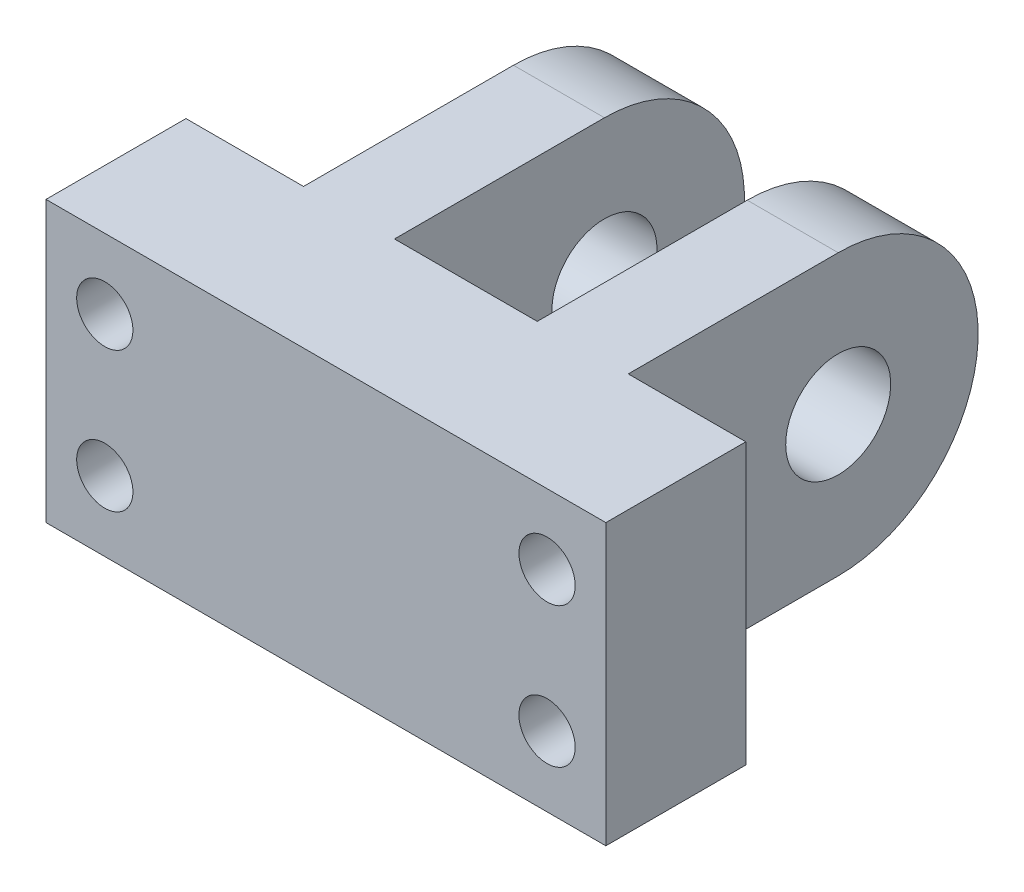
SolidWorks part; units mm, degrees
ref_plane "Front Plane" through (0, 0, 0) normal (0, 0, 1) x (1, 0, 0)
ref_plane "Top Plane" through (0, 0, 0) normal (0, 1, 0) x (1, 0, 0)
ref_plane "Right Plane" through (0, 0, 0) normal (1, 0, 0) x (0, 0, -1)
sketch "Sketch1" plane through (0, 0, 0) normal (1, 0, 0) x (0, 0, -1)
  line L1 (0, 0) -> (31.75, 0)
  line L2 (0, 0) -> (0, 25.4)
  line L3 (0, 25.4) -> (31.75, 25.4)
  circle A0 centre (31.75, 12.7) radius 4.7625
  arc A1 (31.75, 25.4) -> (31.75, 0) centre (31.75, 12.7) cw
  dimension "D1" = 9.525
  dimension "D3" = 12.7
  dimension "D2" = 31.75
extrude "Boss-Extrude1" add sketch "Sketch1" along normal blind 50.8
sketch "Sketch2" plane through (0, 0, 0) normal (0, -1, 0) x (1, 0, 0)
  line L0 (50.8, -12.7) -> (40.132, -12.7)
  line L1 (50.8, 0) -> (50.8, -31.75) construction
  line L2 (40.132, -12.7) -> (40.132, -44.45)
  line L3 (40.132, -44.45) -> (31.877, -44.45)
  line L4 (31.877, -44.45) -> (31.877, -12.7)
  line L5 (31.877, -12.7) -> (18.923, -12.7)
  line L6 (18.923, -12.7) -> (18.923, -44.45)
  line L7 (18.923, -44.45) -> (10.668, -44.45)
  line L8 (10.668, -44.45) -> (10.668, -12.7)
  line L9 (10.668, -12.7) -> (0, -12.7)
  line L10 (0, 0) -> (0, -31.75) construction
  line L11 (40.132, -12.7) -> (31.877, -12.7) construction
  line L12 (18.923, -12.7) -> (10.668, -12.7) construction
  line L13 (50.8, -12.7) -> (50.8, -50.8)
  line L14 (50.8, -50.8) -> (0, -50.8)
  line L15 (0, -50.8) -> (0, -12.7)
  dimension "D1" = 12.954
  dimension "D2" = 8.255
  dimension "D3" = 12.7
  dimension "D4" = 6.35
extrude "Cut-Extrude1" cut sketch "Sketch2" against normal through all
sketch "Sketch3" plane through (0, 0, -12.7) normal (0, 0, -1) x (-1, 0, 0)
  line L0 (-5.334, 25.4) -> (-5.334, 0) construction
  line L1 (-10.668, 25.4) -> (0, 25.4) construction
  line L2 (-10.668, 0) -> (0, 0) construction
  line L3 (-45.466, 0) -> (-45.466, 25.4) construction
  line L4 (-50.8, 0) -> (-40.132, 0) construction
  line L5 (-50.8, 25.4) -> (-40.132, 25.4) construction
  line L6 (-45.466, 19.05) -> (-5.334, 19.05) construction
  line L7 (-5.334, 6.35) -> (-45.466, 6.35) construction
  line L8 (-5.334, 6.35) -> (0, 0) construction
  line L9 (-45.466, 19.05) -> (-50.8, 25.4) construction
  dimension "D1" = 12.7
hole_wizard "CBORE for #10 Socket Head Cap Screw1" positions "Sketch4" profile "Sketch5" counterbore size "#10" standard "ANSI Inch" end condition through all
sketch "Sketch4" plane through (0, 0, -12.7) normal (0, 0, -1) x (-1, 0, 0)
  point P0 (-45.466, 6.35)
  point P3 (-45.466, 19.05)
  point P6 (-5.334, 19.05)
  point P9 (-5.334, 6.35)
sketch "Sketch5" plane through (45.466, 6.35, -12.7) normal (1, 0, 0) x (0, 1, 0)
  line L0 (0, 0) -> (0, 12.7)
  line L1 (0, 12.7) -> (2.5527, 12.7)
  line L3 (2.5527, 12.7) -> (2.5527, 4.826)
  line L4 (2.5527, 4.826) -> (4.7625, 4.826)
  line L5 (4.7625, 4.826) -> (4.7625, 0)
  line L7 (4.7625, 0) -> (0, 0)
  line L11 (0, -6.35) -> (0, 107.95) construction
  dimension "Thru Hole Dia." = 5.1054
  dimension "Thru Hole Depth" = 12.7
  dimension "C'Bore Dia." = 9.525
  dimension "C'Bore Depth" = 4.826
